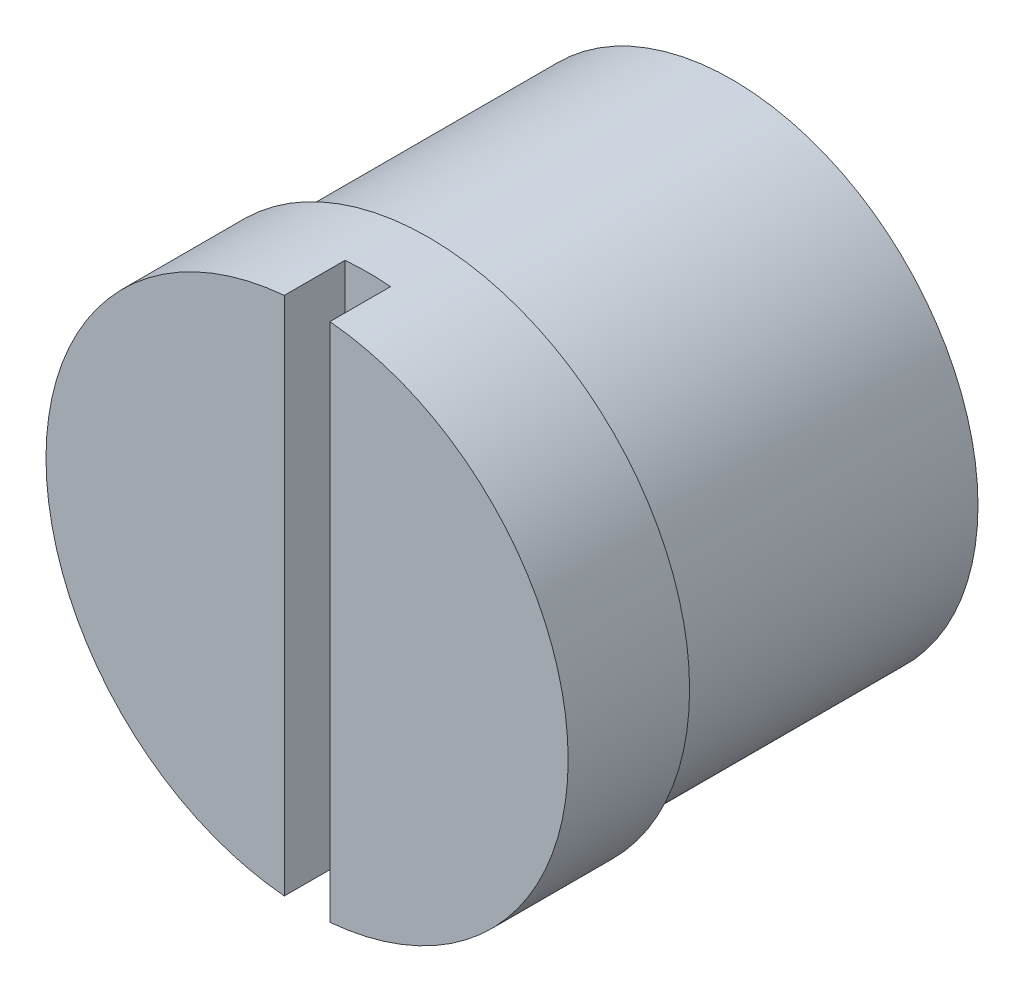
SolidWorks part; units mm, degrees
ref_plane "Front Plane" through (0, 0, 0) normal (0, 0, 1) x (1, 0, 0)
ref_plane "Top Plane" through (0, 0, 0) normal (0, 1, 0) x (1, 0, 0)
ref_plane "Right Plane" through (0, 0, 0) normal (1, 0, 0) x (0, 0, -1)
sketch "Sketch1" plane through (0, 0, 0) normal (0, 0, 1) x (1, 0, 0)
  circle A0 centre (0, 0) radius 2.55
  circle A3 centre (0, 0) radius 2.35 construction
  circle A4 centre (0, 0) radius 4.05
  dimension "D1" = 4.7
  dimension "D2" = 0.2
  dimension "D3" = 1.5
extrude "Boss-Extrude1" add sketch "Sketch1" against normal blind 5
sketch "Sketch2" plane through (0, 0, 0) normal (0, 0, 1) x (1, 0, 0)
  circle A2 centre (0, 0) radius 4.3
  circle A3 centre (0, 0) radius 4.3
  dimension "D1" = 0.25
extrude "Boss-Extrude2" add sketch "Sketch2" along normal blind 2
thread "Thread1" pitch 0.8 method extrude profile "Thread Profile1" start angle 0, offset 0, length 4.5, pitch 0.8, diameter 5.1
ref_plane "Plane1" through (2.55, 0, -5) normal (0, -1, 0) x (1, 0, 0)
sketch "Thread Profile1" plane through (2.55, 0, -5) normal (0, -1, 0) x (1, 0, 0)
  line L0 (0, 0) -> (0, 0.8) construction
  line L11 (0, 0) -> (0, 0.7)
  line L12 (0, 0.7) -> (-0.433, 0.45)
  line L13 (-0.433, 0.45) -> (-0.433, 0.25)
  line L15 (-0.433, 0.25) -> (0, 0)
  line L17 (-0.433, 0.35) -> (0, 0.35) construction
  point P2 (0, 0)
  dimension "Pitch" = 0.8
  dimension "Profile_Angle" = 60
  dimension "Profile_Land" = 0.2
  dimension "Profile_Height" = 0.433
sketch "Sketch3" plane through (0, 0, 2) normal (0, 0, 1) x (1, 0, 0)
  line L0 (0, 4.3) -> (0, -4.3) construction
  line L1 (-0.375, -4.3) -> (0.375, -4.3)
  line L2 (-0.375, 4.3) -> (0.375, 4.3)
  line L3 (0.375, -4.3) -> (0.375, 4.3)
  line L4 (-0.375, 4.3) -> (-0.375, -4.3)
  circle A0 centre (0, 0) radius 4.3 construction
  point P7 (0, 0)
  point P11 (0, -4.3)
  point P14 (0, 4.3)
  dimension "D1" = 0.75
extrude "Cut-Extrude1" cut sketch "Sketch3" against normal blind 1
equation "\"ThreadWalls\"= 1.5"
equation "\"D3@Sketch1\"=\"ThreadWalls\""
equation "\"BaseFlange\"= 0.25"
equation "\"D1@Sketch2\"=\"BaseFlange\""
